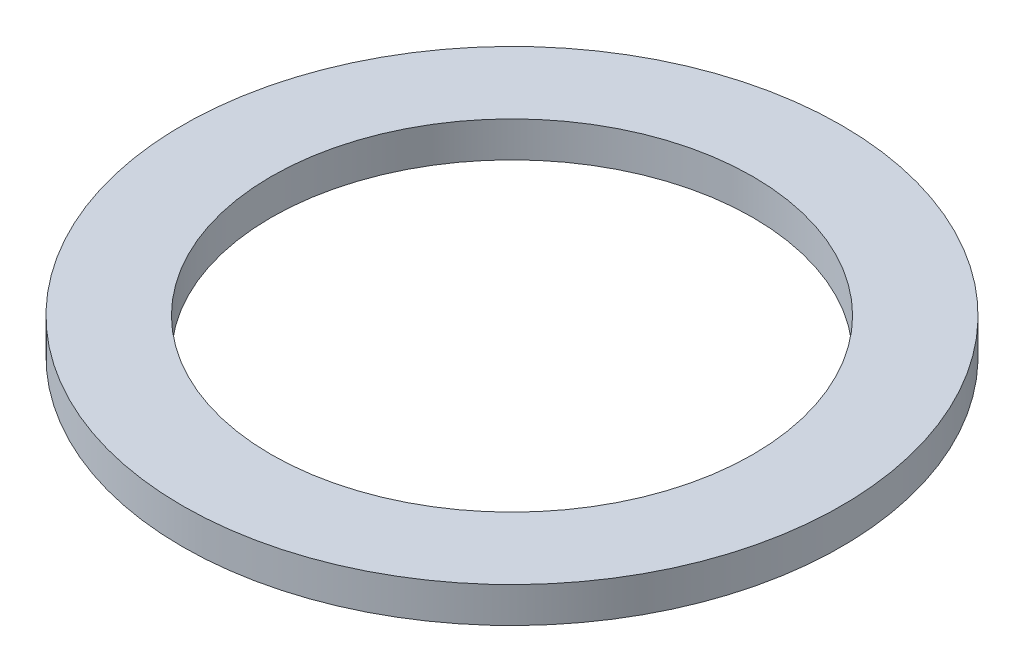
SolidWorks part; units mm, degrees
ref_plane "Front Plane" through (0, 0, 0) normal (0, 0, 1) x (1, 0, 0)
ref_plane "Top Plane" through (0, 0, 0) normal (0, 1, 0) x (1, 0, 0)
ref_plane "Right Plane" through (0, 0, 0) normal (1, 0, 0) x (0, 0, -1)
sketch "Sketch1" plane through (0, 0, 0) normal (0, 1, 0) x (1, 0, 0)
  circle A0 centre (0, 0) radius 65
  dimension "FLANGE_OD" = 130
extrude "Boss-Extrude1" add sketch "Sketch1" along normal blind 7
sketch "Sketch2" plane through (0, 0, 0) normal (0, 1, 0) x (1, 0, 0)
  circle A0 centre (0, 0) radius 47.5
  dimension "BORE_D" = 95
extrude "Cut-Extrude1" cut sketch "Sketch2" along normal through all
sketch "Sketch3" plane through (0, 7, 0) normal (0, 1, 0) x (1, 0, 0)
  circle A0 centre (0, 0) radius 26.6684 construction
  circle A1 centre (-26.6684, 0) radius 2.8678
  dimension "BOLT_D" = 5.7357
  dimension "BOLT_PCD" = 53.3368
extrude "Cut-Extrude2" cut sketch "Sketch3" against normal blind 6.5979 rebuild error yes
pattern_circular "CirPattern1" count 8 over 360 rebuild error yes
